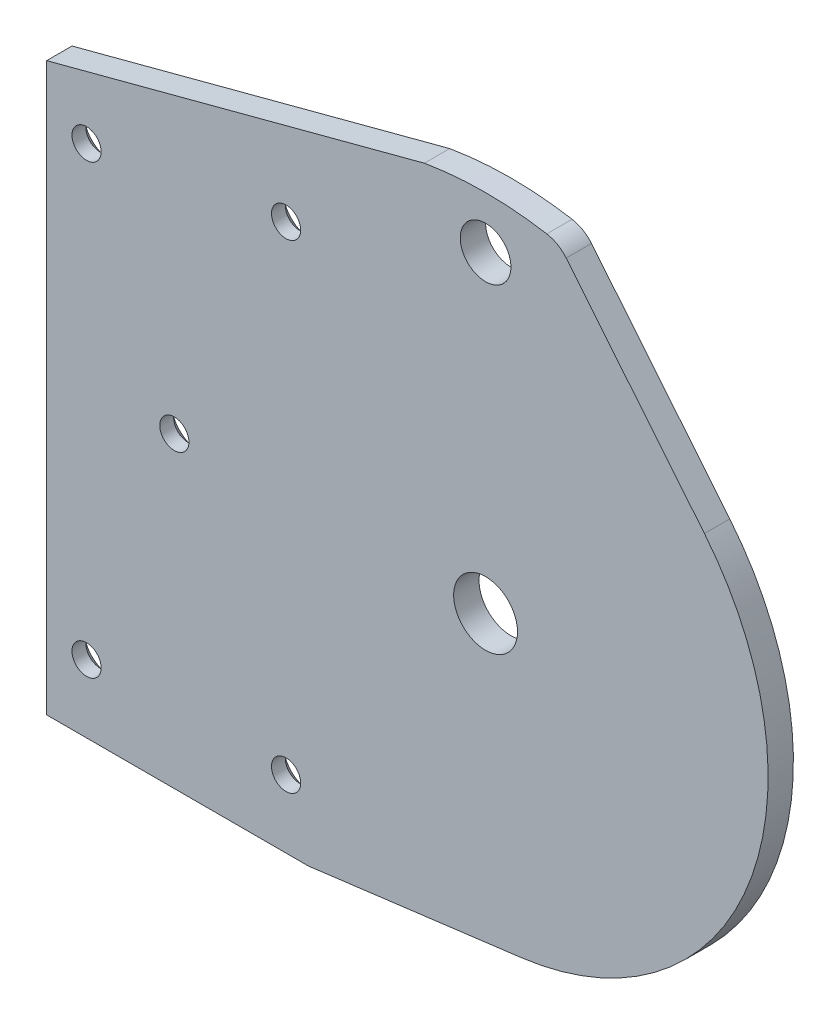
SolidWorks part; units mm, degrees
material "6061-T6 (SS)"
ref_plane "Front" through (0, 0, 0) normal (0, 0, 1) x (1, 0, 0)
ref_plane "Top" through (0, 0, 0) normal (0, 1, 0) x (1, 0, 0)
ref_plane "Right" through (0, 0, 0) normal (1, 0, 0) x (0, 0, -1)
ref_axis "side-side" through (80.9, 0, 0) along (-1, 0, 0)
ref_axis "up-down" through (0, 50, 0) along (0, -1, 0)
ref_axis "front-back" through (0, 0, -80.9) along (0, 0, 1)
sketch "Sketch1" plane through (0, 0, 0) normal (0, 0, 1) x (1, 0, 0)
  line L1 (-55, -38.5098) -> (-22.1991, -38.5098)
  line L6 (-55, 32.4912) -> (-55, -38.5098)
  line L7 (-22.1991, -38.5098) -> (4.4679, -35.1169)
  line L8 (0, 0) -> (-57.9253, 0) construction
  line L11 (-55, 32.4912) -> (-7.6719, 45.0261)
  line L12 (10.0989, 43.6121) -> (27.425, 22.3836)
  circle A10 centre (0, 39.175) radius 3.175
  arc A12 (4.4679, -35.1169) -> (27.425, 22.3836) centre (0, 0) ccw
  arc A18 (7.6719, 45.0261) -> (-7.6719, 45.0261) centre (0, 0) ccw
  arc A19 (10.0989, 43.6121) -> (7.6719, 45.0261) centre (7, 41.0829) ccw
  circle A21 centre (0, 0) radius 4
  arc A22 (-16.4246, 31.3591) -> (-21.3668, -28.2245) centre (0, 0) ccw construction
  dimension "D1" = 39.175
  dimension "D3" = 6.35
  dimension "D5" = 35.4
  dimension "D9" = 8
  dimension "D2" = 90
  dimension "D4" = 55
  dimension "D6" = 32.4912
  dimension "D7" = 38.5098
  dimension "D8" = 22.1991
extrude "Boss-Extrude1" add sketch "Sketch1" against normal blind 3.175
hole_wizard "CSK for #6 Flat Head Machine Screw (100)1" positions "Sketch3" profile "Sketch4" countersink size "#6" standard "ANSI Inch"
sketch "Sketch3" plane through (0, 0, -3.175) normal (0, 0, -1) x (-1, 0, 0)
  line L0 (0, 0) -> (57.9253, 0) construction
  point P0 (50, 26)
  point P2 (39, 0)
  point P4 (50, -30)
  point P11 (25, 30)
  point P24 (25, -30)
  point P33 (32, -24)
  point P34 (0, 0)
  dimension "D1" = 39
  dimension "D2" = 30
  dimension "D3" = 26
  dimension "D4" = 30
  dimension "25" = 25
  dimension "D6" = 30
  dimension "D7" = 50
sketch "Sketch4" plane through (-50, 26, -3.175) normal (1, 0, 0) x (0, 1, 0)
  line L0 (0, 0) -> (0, 9.0989)
  line L1 (0, 9.0989) -> (1.8288, 8)
  line L2 (1.8288, 8) -> (1.8288, 1.4386)
  line L3 (1.8288, 1.4386) -> (3.5433, 0)
  line L5 (3.5433, 0) -> (0, 0)
  line L6 (-1.8288, 1.4386) -> (-3.5433, 0) construction
  line L10 (0, 9.0989) -> (-1.8288, 8) construction
  line L11 (0, -6.35) -> (0, 107.95) construction
  dimension "Hole Dia." = 3.6576
  dimension "Hole Depth" = 8
  dimension "Near C'Sink Dia." = 7.0866
  dimension "Near C'Sink Angle" = 100
  dimension "Drill Angle" = 118
